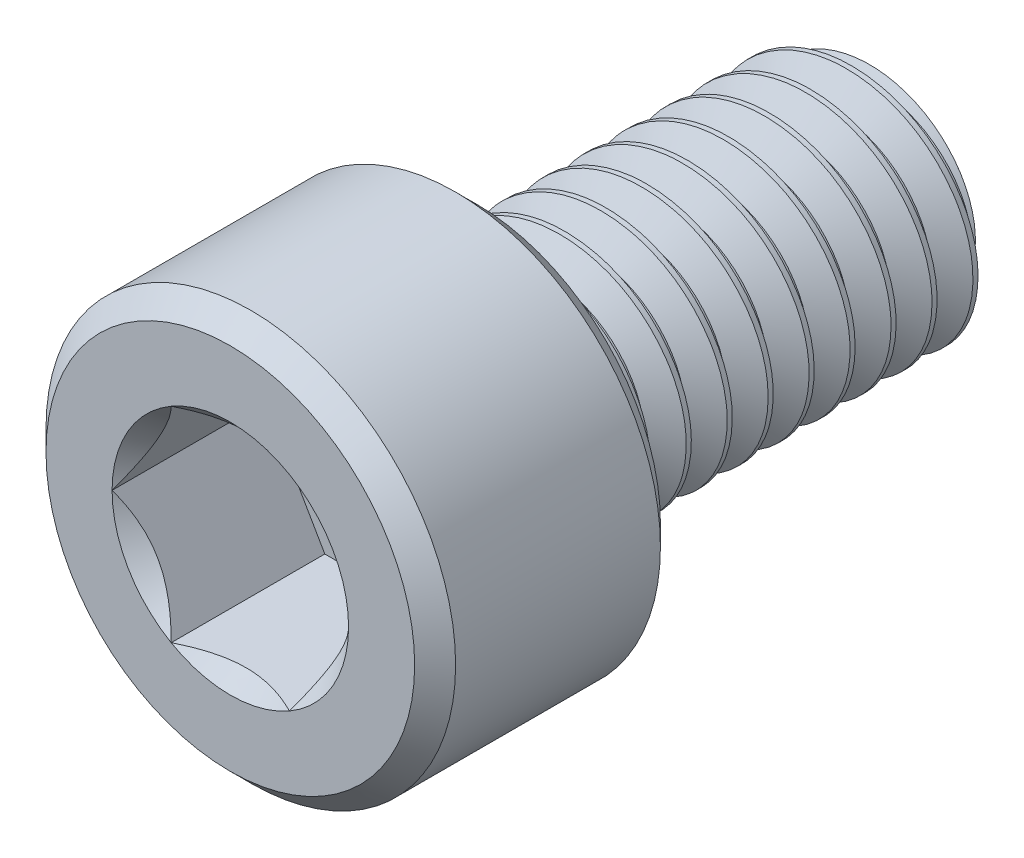
SolidWorks part; units mm, degrees
ref_plane "Front Plane" through (0, 0, 0) normal (0, 0, 1) x (1, 0, 0)
ref_plane "Top Plane" through (0, 0, 0) normal (0, 1, 0) x (1, 0, 0)
ref_plane "Right Plane" through (0, 0, 0) normal (1, 0, 0) x (0, 0, -1)
sketch "Sketch1" plane through (0, 0, 0) normal (0, 0, 1) x (1, 0, 0)
  circle A0 centre (0, 0) radius 3
  dimension "BODY DIAMETER" = 6
extrude "Boss-Extrude1" add sketch "Sketch1" along normal blind 10
sketch "Sketch2" plane through (0, 0, 0) normal (0, 0, -1) x (-1, 0, 0)
  circle A1 centre (0, 0) radius 3
  circle A2 centre (0, 0) radius 3
  dimension "D1" = 0
curve "Helix/Spiral1" pitch 1 height 45 turns 45 parameters "PITCH"=1
ref_plane "Plane1" through (0, 3, 0) normal (-0.9986, 0, 0.053) x (0.053, 0, 0.9986)
sketch "Sketch3" plane through (0, 3, 0) normal (-0.9986, 0, 0.053) x (0.053, 0, 0.9986)
  line L0 (0, 0) -> (-0.875, 0)
  line L1 (-0.875, 0) -> (-0.5, -0.6495)
  line L2 (-0.5, -0.6495) -> (-0.375, -0.6495)
  line L3 (-0.375, -0.6495) -> (0, 0)
  line L4 (-0.4375, -0.6495) -> (-0.4375, 0) construction
  line L5 (-0.6875, -0.3248) -> (-0.1875, -0.3248) construction
  dimension "D1" = 60
  dimension "THREAD DIM1" = 0.125
  dimension "THREAD DIM 2" = 0.5
sweep "Cut-Sweep1" cut profiles "Sketch3" path "Helix/Spiral1" align with end faces yes
sketch "Sketch4" plane through (0, 0, 0) normal (1, 0, 0) x (0, 0, -1)
  line L0 (0, 4) -> (-1.3329, 4)
  line L1 (-1.3329, 4) -> (0, 2.0965)
  line L2 (0, 2.0965) -> (0, 4)
  line L3 (0, 3) -> (0.8738, 3) construction
  line L4 (0, 0) -> (1.7976, 0) construction
  dimension "D1" = 55
  dimension "D2" = 1
  dimension "D3" = 0.254
revolve "Cut-Revolve1" cut sketch "Sketch4" angle 360 about L4
sketch "Sketch5" plane through (0, 0, 10) normal (0, 0, 1) x (1, 0, 0)
  circle A0 centre (0, 0) radius 5
  dimension "HEAD DIAMETER" = 10
extrude "Boss-Extrude2" add sketch "Sketch5" along normal blind 6
sketch "Sketch6" plane through (0, 0, 16) normal (0, 0, 1) x (1, 0, 0)
  line L1 (1.4434, 2.5) -> (-1.4434, 2.5)
  line L2 (-1.4434, 2.5) -> (-2.8868, 0)
  line L3 (-2.8868, 0) -> (-1.4434, -2.5)
  line L4 (-1.4434, -2.5) -> (1.4434, -2.5)
  line L5 (1.4434, -2.5) -> (2.8868, 0)
  line L6 (2.8868, 0) -> (1.4434, 2.5)
  circle A0 centre (0, 0) radius 2.5 construction
  dimension "HEX SOCKET SIZE" = 5
extrude "Cut-Extrude1" cut sketch "Sketch6" against normal blind 3.75
sketch "Sketch7" plane through (0, 0, 16) normal (0, 0, 1) x (1, 0, 0)
  circle A0 centre (0, 0) radius 2.8868
extrude "Cut-Extrude2" cut sketch "Sketch7" against normal through all draft 45
chamfer "Chamfer1" distance 0.5 angle 45 2 edges at (5, 0, 10) (5, 0, 16)
